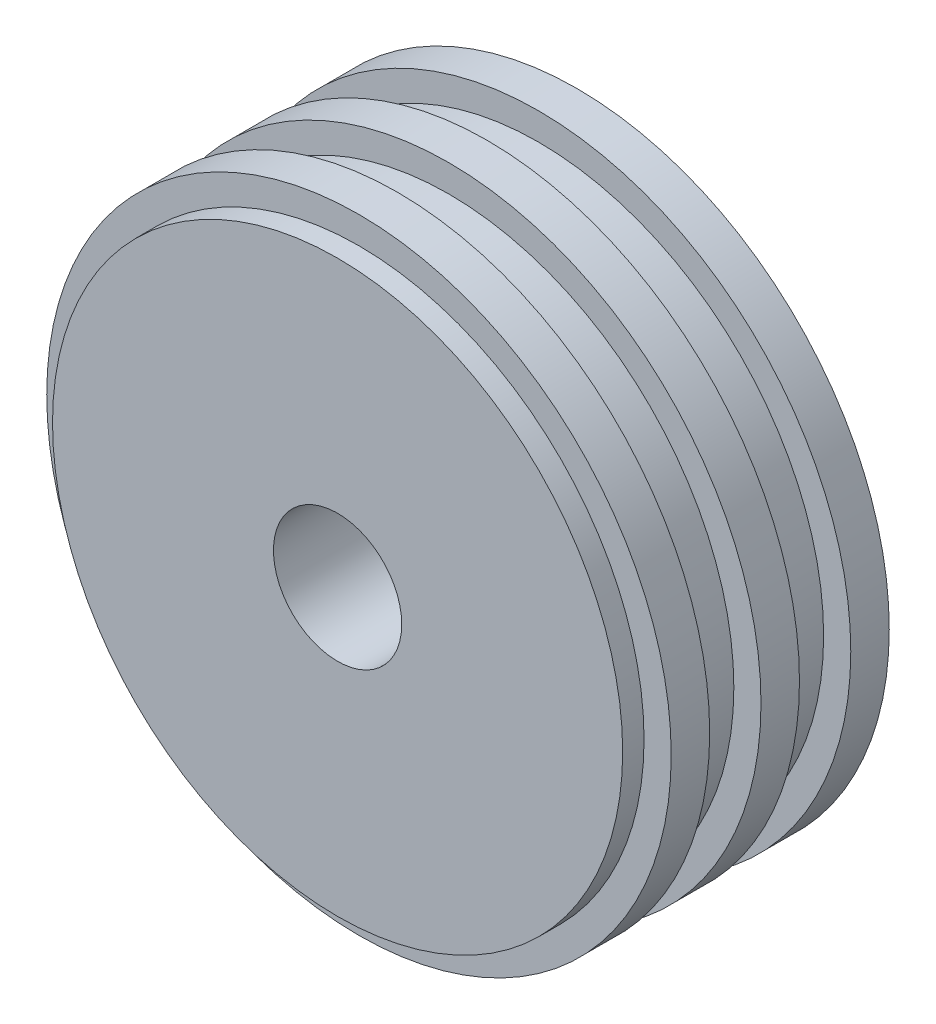
SolidWorks part; units mm, degrees
ref_plane "Front Plane" through (0, 0, 0) normal (0, 0, 1) x (1, 0, 0)
ref_plane "Top Plane" through (0, 0, 0) normal (0, 1, 0) x (1, 0, 0)
ref_plane "Right Plane" through (0, 0, 0) normal (1, 0, 0) x (0, 0, -1)
sketch "Sketch1" plane through (0, 0, 0) normal (0, 0, 1) x (1, 0, 0)
  circle A0 centre (0, 0) radius 66.675
  circle A1 centre (0, 0) radius 15
  dimension "D1" = 133.35
  dimension "D2" = 30
extrude "Boss-Extrude1" add sketch "Sketch1" against normal blind 57
ref_plane "Plane1" through (0, 0, -5) normal (0, 0, 1) x (1, 0, 0)
sketch "Sketch2" plane through (0, 0, -5) normal (0, 0, 1) x (1, 0, 0)
  circle A0 centre (0, 0) radius 73.025
  dimension "D1" = 146.05
extrude "Boss-Extrude2" add sketch "Sketch2" against normal blind 9
ref_axis "Axis1" through (0, 0, -5.6629) along (0, 0, 1)
sketch "Sketch4" plane through (0, 0, -5) normal (0, 0, 1) x (1, 0, 0)
sketch "Sketch5" plane through (0, 0, -5) normal (0, 0, 1) x (1, 0, 0)
  circle A0 centre (0, 0) radius 15
extrude "Cut-Extrude1" cut sketch "Sketch5" against normal through all
ref_axis "Axis2" through (0, 0, -57) along (0, 0, 1)
ref_axis "Axis3" through (0, 0, -57) along (0, 0, 1)
pattern_linear "LPattern3" count 3 spacing 21 along (0, 0, -1) of "Boss-Extrude2"
